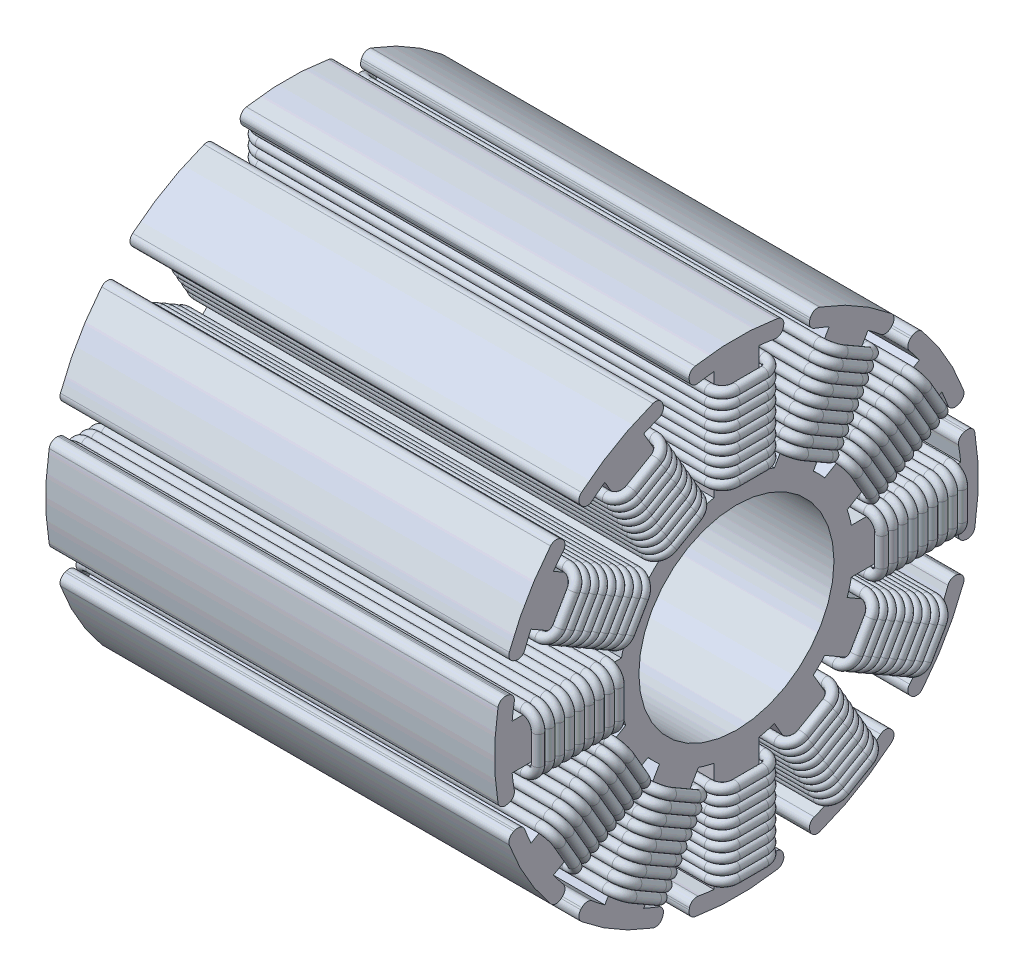
SolidWorks part; units mm, degrees
ref_plane "Front Plane" through (0, 0, 0) normal (0, 0, 1) x (1, 0, 0)
ref_plane "Top Plane" through (0, 0, 0) normal (0, 1, 0) x (1, 0, 0)
ref_plane "Right Plane" through (0, 0, 0) normal (1, 0, 0) x (0, 0, -1)
sketch "Sketch1" plane through (0, 0, 0) normal (1, 0, 0) x (0, 0, -1)
  circle A0 centre (0, 0) radius 12
  dimension "D1" = 24
extrude "Boss-Extrude1" add sketch "Sketch1" along normal blind 46
sketch "Sketch2" plane through (46, 0, 0) normal (1, 0, 0) x (0, 0, -1)
  line L0 (0, 0) -> (0, 12) construction
  line L1 (0, 12) -> (0, 25.7143) construction
  line L2 (0, 0) -> (-4.6573, 22.6256) construction
  line L3 (-4.6573, 22.6256) -> (-5.1765, 25.1483) construction
  line L4 (-5, 24.2907) -> (-4.6573, 22.6256)
  line L5 (-2.3, 22.9852) -> (-2.3, 11.7775)
  line L6 (2.3, 22.9852) -> (2.3, 11.7775)
  line L7 (2.3, 22.9852) -> (2.3, 11.7775)
  line L8 (5, 24.2907) -> (4.6573, 22.6256)
  line L9 (7.8152, 23.5364) -> (7.2795, 21.923)
  line L10 (16.4755, 18.5364) -> (15.3461, 17.2658)
  line L11 (9.5007, 21.0558) -> (3.8969, 11.3496)
  line L12 (13.4845, 18.7558) -> (7.8806, 9.0496)
  line L13 (18.5364, 16.4755) -> (17.2658, 15.3461)
  line L14 (23.5364, 7.8152) -> (21.923, 7.2795)
  line L15 (18.7558, 13.4845) -> (9.0496, 7.8806)
  line L16 (21.0558, 9.5007) -> (11.3496, 3.8969)
  line L17 (24.2907, 5) -> (22.6256, 4.6573)
  line L18 (24.2907, -5) -> (22.6256, -4.6573)
  line L19 (22.9852, 2.3) -> (11.7775, 2.3)
  line L20 (22.9852, -2.3) -> (11.7775, -2.3)
  line L21 (23.5364, -7.8152) -> (21.923, -7.2795)
  line L22 (18.5364, -16.4755) -> (17.2658, -15.3461)
  line L23 (21.0558, -9.5007) -> (11.3496, -3.8969)
  line L24 (18.7558, -13.4845) -> (9.0496, -7.8806)
  line L25 (16.4755, -18.5364) -> (15.3461, -17.2658)
  line L26 (7.8152, -23.5364) -> (7.2795, -21.923)
  line L27 (13.4845, -18.7558) -> (7.8806, -9.0496)
  line L28 (9.5007, -21.0558) -> (3.8969, -11.3496)
  line L29 (5, -24.2907) -> (4.6573, -22.6256)
  line L30 (-5, -24.2907) -> (-4.6573, -22.6256)
  line L31 (2.3, -22.9852) -> (2.3, -11.7775)
  line L32 (-2.3, -22.9852) -> (-2.3, -11.7775)
  line L33 (-7.8152, -23.5364) -> (-7.2795, -21.923)
  line L34 (-16.4755, -18.5364) -> (-15.3461, -17.2658)
  line L35 (-9.5007, -21.0558) -> (-3.8969, -11.3496)
  line L36 (-13.4845, -18.7558) -> (-7.8806, -9.0496)
  line L37 (-18.5364, -16.4755) -> (-17.2658, -15.3461)
  line L38 (-23.5364, -7.8152) -> (-21.923, -7.2795)
  line L39 (-18.7558, -13.4845) -> (-9.0496, -7.8806)
  line L40 (-21.0558, -9.5007) -> (-11.3496, -3.8969)
  line L41 (-24.2907, -5) -> (-22.6256, -4.6573)
  line L42 (-24.2907, 5) -> (-22.6256, 4.6573)
  line L43 (-22.9852, -2.3) -> (-11.7775, -2.3)
  line L44 (-22.9852, 2.3) -> (-11.7775, 2.3)
  line L45 (-23.5364, 7.8152) -> (-21.923, 7.2795)
  line L46 (-18.5364, 16.4755) -> (-17.2658, 15.3461)
  line L47 (-21.0558, 9.5007) -> (-11.3496, 3.8969)
  line L48 (-18.7558, 13.4845) -> (-9.0496, 7.8806)
  line L49 (-16.4755, 18.5364) -> (-15.3461, 17.2658)
  line L50 (-7.8152, 23.5364) -> (-7.2795, 21.923)
  line L51 (-13.4845, 18.7558) -> (-7.8806, 9.0496)
  line L52 (-9.5007, 21.0558) -> (-3.8969, 11.3496)
  circle A0 centre (0, 0) radius 12 construction
  arc A1 (-4.6573, 22.6256) -> (4.6573, 22.6256) centre (0, 0) cw
  arc A2 (-5, 24.2907) -> (5, 24.2907) centre (0, 0) cw
  arc A3 (7.8152, 23.5364) -> (16.4755, 18.5364) centre (0, 0) cw
  arc A4 (7.2795, 21.923) -> (15.3461, 17.2658) centre (0, 0) cw
  arc A5 (18.5364, 16.4755) -> (23.5364, 7.8152) centre (0, 0) cw
  arc A6 (17.2658, 15.3461) -> (21.923, 7.2795) centre (0, 0) cw
  arc A7 (24.2907, 5) -> (24.2907, -5) centre (0, 0) cw
  arc A8 (22.6256, 4.6573) -> (22.6256, -4.6573) centre (0, 0) cw
  arc A9 (23.5364, -7.8152) -> (18.5364, -16.4755) centre (0, 0) cw
  arc A10 (21.923, -7.2795) -> (17.2658, -15.3461) centre (0, 0) cw
  arc A11 (16.4755, -18.5364) -> (7.8152, -23.5364) centre (0, 0) cw
  arc A12 (15.3461, -17.2658) -> (7.2795, -21.923) centre (0, 0) cw
  arc A13 (5, -24.2907) -> (-5, -24.2907) centre (0, 0) cw
  arc A14 (4.6573, -22.6256) -> (-4.6573, -22.6256) centre (0, 0) cw
  arc A15 (-7.8152, -23.5364) -> (-16.4755, -18.5364) centre (0, 0) cw
  arc A16 (-7.2795, -21.923) -> (-15.3461, -17.2658) centre (0, 0) cw
  arc A17 (-18.5364, -16.4755) -> (-23.5364, -7.8152) centre (0, 0) cw
  arc A18 (-17.2658, -15.3461) -> (-21.923, -7.2795) centre (0, 0) cw
  arc A19 (-24.2907, -5) -> (-24.2907, 5) centre (0, 0) cw
  arc A20 (-22.6256, -4.6573) -> (-22.6256, 4.6573) centre (0, 0) cw
  arc A21 (-23.5364, 7.8152) -> (-18.5364, 16.4755) centre (0, 0) cw
  arc A22 (-21.923, 7.2795) -> (-17.2658, 15.3461) centre (0, 0) cw
  arc A23 (-16.4755, 18.5364) -> (-7.8152, 23.5364) centre (0, 0) cw
  arc A24 (-15.3461, 17.2658) -> (-7.2795, 21.923) centre (0, 0) cw
  point P106 (0, 0)
  circle M4 centre (0, 0) radius 12
  dimension "D1" = 1.7
  dimension "D2" = 12
  dimension "D3" = 5
  dimension "D4" = 2.3
extrude "Boss-Extrude2" add sketch "Sketch2" against normal blind 46 contours A24 L51 L52 M4 | L49 A24 L50 A23 | L45 A22 L46 A21 | A22 L47 L48 M4 | A20 L43 L44 M4 | L41 A20 L42 A19 | A18 L39 L40 M4 | A16 L35 L36 M4 | L29 A14 L30 A13 | A14 L31 L32 M4 | A12 L27 L28 M4 | A10 L23 L24 M4 | L21 A10 L22 A9 | A8 L18 A7 L17 | A8 L19 L20 M4 | A6 L15 L16 M4 | L13 A6 L14 A5 | L9 A4 L10 A3 | A4 L11 L12 M4 | A2 L4 A1 L8 | A1 L5 L6 M4 | A18 L38 A17 L37 | A16 L34 A15 L33 | A12 L26 A11 L25 region at (46, 23.7958, 0) region at (46, 17.4938, 0) region at (46, 15.1501, 8.7469) region at (46, 15.1501, -8.7469) region at (46, 20.6078, 11.8979) region at (46, 20.6078, -11.8979) region at (46, 8.7469, 15.1501) region at (46, 8.7469, -15.1501) region at (46, 11.8979, 20.6078) region at (46, 11.8979, -20.6078) region at (46, 0, 17.4938) region at (46, 0, -17.4938) region at (46, 0, 23.7958) region at (46, 0, -23.7958) region at (46, -8.7469, 15.1501) region at (46, -8.7469, -15.1501) region at (46, -15.1501, 8.7469) region at (46, -11.8979, -20.6078) region at (46, -15.1501, -8.7469) region at (46, -17.4938, 0) region at (46, -23.7958, 0)
fillet "Fillet1" radius 0.762 47 edges at (23, 17.2658, 15.3461) (23, 21.923, 7.2795) (23, 23.5364, 7.8152) (23, 18.5364, 16.4755) (23, 15.3461, 17.2658) (23, 16.4755, 18.5364) (23, 7.2795, 21.923) (23, 7.8152, 23.5364) (23, 4.6573, 22.6256) (23, 5, 24.2907) (23, -5, 24.2907) (23, -4.6573, 22.6256) (23, -15.3461, 17.2658) (23, -7.2795, 21.923) (23, -7.8152, 23.5364) (23, -16.4755, 18.5364) (23, -17.2658, 15.3461) (23, -18.5364, 16.4755) (23, -21.923, 7.2795) (23, -23.5364, 7.8152) (23, -24.2907, 5) (23, -22.6256, 4.6573) (23, -24.2907, -5) (23, -22.6256, -4.6573) (23, -23.5364, -7.8152) (23, -21.923, -7.2795) (23, -18.5364, -16.4755) (23, -17.2658, -15.3461) (23, -16.4755, -18.5364) (23, -15.3461, -17.2658) (23, -7.8152, -23.5364) (23, -7.2795, -21.923) (23, -5, -24.2907) (23, -4.6573, -22.6256) (23, 4.6573, -22.6256) (23, 5, -24.2907) (23, 7.2795, -21.923) (23, 7.8152, -23.5364) (23, 15.3461, -17.2658) (23, 16.4755, -18.5364) (23, 22.6256, -4.6573) (23, 17.2658, -15.3461) (23, 18.5364, -16.4755) (23, 21.923, -7.2795) (23, 24.2907, -5) (23, 22.6256, 4.6573) (23, 24.2907, 5)
sketch "Sketch3" plane through (46, 0, 0) normal (1, 0, 0) x (0, 0, -1)
  circle A0 centre (0, 0) radius 10
  dimension "D1" = 20
extrude "Cut-Extrude1" cut sketch "Sketch3" against normal through all
fillet "Fillet2" radius 0.762 1 edges at (23, 23.5364, -7.8152)
ref_plane "Plane1" through (0, 10.1996, 5.8888) normal (0, -0.866, -0.5) x (1, 0, 0)
sketch "Sketch5" plane through (0, 10.1996, 5.8888) normal (0, -0.866, -0.5) x (1, 0, 0)
  line L0 (46, -2.3) -> (0, -2.3)
  line L1 (0, 2.3) -> (46, 2.3)
  line L2 (23, 2.3) -> (23, -2.3) construction
  line L3 (0, 2.3) -> (0, -2.3) construction
  line L4 (23, 0) -> (0, 0) construction
  line L5 (0, 0) -> (-1.1036, 0) construction
  line L6 (-0.842, 1.458) -> (-0.842, -1.458)
  line L7 (46.842, 1.458) -> (46.842, -1.458)
  arc A0 (0, 2.3) -> (-0.842, 1.458) centre (0, 1.458) ccw
  arc A1 (0, -2.3) -> (-0.842, -1.458) centre (0, -1.458) cw
  arc A2 (46, -2.3) -> (46.842, -1.458) centre (46, -1.458) ccw
  arc A3 (46, 2.3) -> (46.842, 1.458) centre (46, 1.458) cw
  point P18 (-0.842, 0)
sketch "Sketch6" plane through (0, 0, 0) normal (-1, 0, 0) x (0, 0, 1)
  line L0 (13.4845, 18.7558) -> (7.8806, 9.0496) construction
  circle A0 centre (9.1879, 10.3233) radius 0.4953
  circle A1 centre (9.6959, 11.2032) radius 0.4953
  circle A2 centre (10.2039, 12.0831) radius 0.4953
  circle A3 centre (10.7119, 12.9629) radius 0.4953
  circle A4 centre (11.2199, 13.8428) radius 0.4953
  circle A5 centre (11.7279, 14.7227) radius 0.4953
  circle A6 centre (12.2359, 15.6026) radius 0.4953
  circle A7 centre (12.7439, 16.4825) radius 0.4953
  circle A8 centre (13.2519, 17.3623) radius 0.4953
  dimension "D1" = 0.9906
  dimension "D2" = 9
sweep "Sweep1" add profiles "Sketch6" path "Sketch5"
pattern_circular "CirPattern8" count 12 over 360 of bodies 105 106 107 108 109 110 111 112 113
